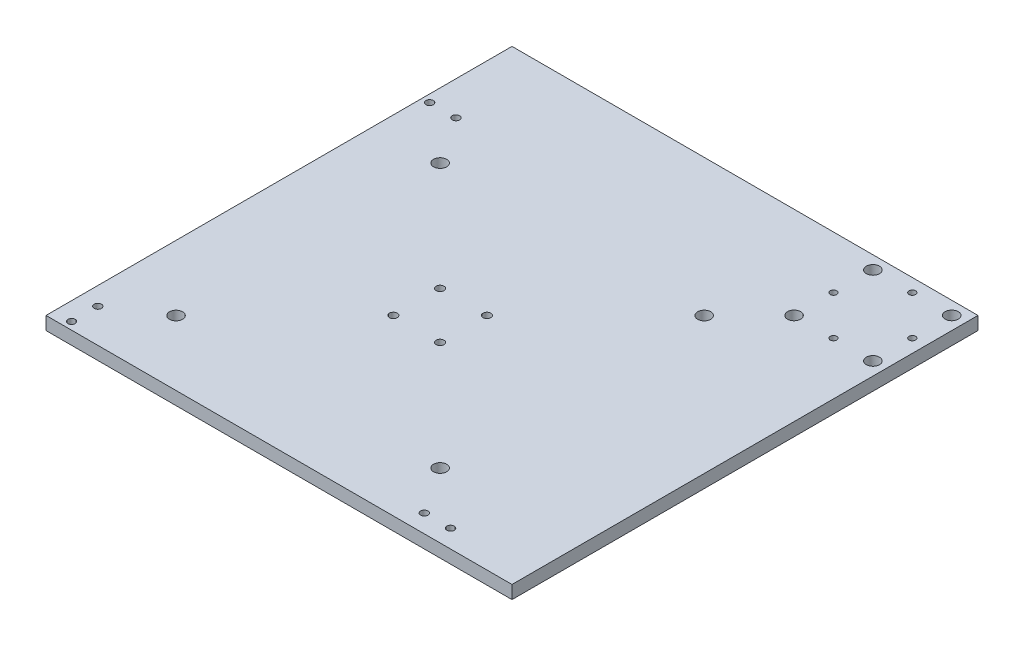
SolidWorks part; units mm, degrees
material "Perspex (TM) GS Acrylic Cast Sheet"
ref_plane "Front Plane" through (0, 0, 0) normal (0, 0, 1) x (1, 0, 0)
ref_plane "Top Plane" through (0, 0, 0) normal (0, 1, 0) x (1, 0, 0)
ref_plane "Right Plane" through (0, 0, 0) normal (1, 0, 0) x (0, 0, -1)
sketch "Sketch1" plane through (0, 0, 0) normal (0, 1, 0) x (1, 0, 0)
  line L1 (-95.25, -95.25) -> (95.25, -95.25)
  line L2 (-95.25, -95.25) -> (-95.25, 95.25)
  line L3 (-95.25, 95.25) -> (95.25, 95.25)
  line L4 (95.25, -95.25) -> (95.25, 95.25)
  line L5 (-15.875, -15.875) -> (15.875, -15.875)
  line L6 (-15.875, -15.875) -> (-15.875, 15.875)
  line L7 (-15.875, 15.875) -> (15.875, 15.875)
  line L8 (15.875, -15.875) -> (15.875, 15.875)
  circle A0 centre (-11.303, 11.303) radius 1.905
  circle A1 centre (-11.303, -11.303) radius 1.905
  circle A2 centre (11.303, 11.303) radius 1.905
  circle A3 centre (11.303, -11.303) radius 1.905
  circle A4 centre (-78.9, 86.55) radius 1.778
  circle A5 centre (-91.6, 86.55) radius 1.778
  circle A6 centre (91.6, -86.55) radius 1.778
  circle A7 centre (78.9, -86.55) radius 1.778
  circle A8 centre (-86.55, -78.9) radius 1.778
  circle A9 centre (-86.55, -91.6) radius 1.778
  circle A10 centre (0, 0) radius 6.35
  point P0 (0, 0)
  point P6 (0, 0)
  point P19 (-85.25, 92.9)
  point P24 (85.25, -92.9)
  point P29 (-92.9, -85.25)
  dimension "D5" = 4.572
  dimension "D10" = 12.7
  dimension "D18" = 12.7
  dimension "D1" = 190.5
  dimension "D2" = 190.5
  dimension "D3" = 31.75
  dimension "D4" = 31.75
  dimension "D6" = 4.572
  dimension "D7" = 4.572
  dimension "D8" = 92.9
  dimension "D9" = 85.25
  dimension "D11" = 4.572
  dimension "D12" = 6.35
  dimension "D13" = 6.35
  dimension "D14" = 92.9
  dimension "D15" = 85.25
  dimension "D16" = 6.35
  dimension "D17" = 6.35
  dimension "D19" = 85.25
  dimension "D20" = 92.9
  dimension "D21" = 6.35
  dimension "D22" = 6.35
  dimension "D23" = 12.7
extrude "Boss-Extrude1" add sketch "Sketch1" along normal blind 6.35 contours L4 L3 L2 L1 | A7 | A6 | A8 | A9 | A4 | A5 | A1 | A3 | A0 | A2
sketch "Sketch7" plane through (0, 0, 0) normal (0, -1, 0) x (1, 0, 0)
  line L0 (-130, -130) -> (78.2, -130) construction
  line L1 (130, -78.2) -> (130, 130) construction
  line L2 (-95.25, -130) -> (78.2, -130)
  line L3 (130, -78.2) -> (130, 95.25)
  line L4 (130, -78.2) -> (130, -130)
  line L5 (130, -130) -> (78.2, -130)
  line L6 (-95.25, -95.25) -> (-95.25, -130)
  line L7 (-95.25, -95.25) -> (95.25, -95.25)
  line L8 (95.25, -95.25) -> (95.25, 95.25)
  line L9 (95.25, 95.25) -> (130, 95.25)
extrude "Boss-Extrude3" add sketch "Sketch7" against normal up to surface (6.35 mm away) contours L2 L5 L4 L3 L9 L8 L7 L6 up to face at (-11.303, 6.35, -9.398)
sketch "Sketch8" plane through (0, 0, 0) normal (0, -1, 0) x (1, 0, 0)
  circle A0 centre (-63.7786, -63.7786) radius 3.175 construction
  circle A1 centre (-63.7786, 63.8746) radius 3.175 construction
  circle A2 centre (63.8746, 63.8746) radius 3.175 construction
  circle A3 centre (63.8746, -63.7786) radius 3.175 construction
  circle A4 centre (-63.7786, -63.7786) radius 3.175
  circle A5 centre (-63.7786, 63.8746) radius 3.175
  circle A6 centre (63.8746, 63.8746) radius 3.175
  circle A7 centre (63.8746, -63.7786) radius 3.175
extrude "Cut-Extrude1" cut sketch "Sketch8" against normal through all
sketch "Sketch9" plane through (0, 0, 0) normal (0, -1, 0) x (1, 0, 0)
  circle A0 centre (123.65, -123.65) radius 3.175 construction
  circle A1 centre (85.55, -85.55) radius 3.175 construction
  circle A2 centre (123.65, -85.55) radius 3.175 construction
  circle A3 centre (123.65, -123.65) radius 3.175
  circle A4 centre (85.55, -85.55) radius 3.175
  circle A5 centre (123.65, -85.55) radius 3.175
  circle A7 centre (85.55, -123.65) radius 3.175
  circle A8 centre (85.55, -123.65) radius 3.175
  dimension "D1" = 0
extrude "Cut-Extrude2" cut sketch "Sketch9" against normal through all
sketch "Sketch10" plane through (0, 0, 0) normal (0, -1, 0) x (1, 0, 0)
  circle A0 centre (104.6, -123.65) radius 1.5875 construction
  circle A1 centre (85.55, -104.6) radius 1.5875 construction
  circle A2 centre (104.6, -85.55) radius 1.5875 construction
  circle A3 centre (123.65, -104.6) radius 1.5875 construction
  circle A4 centre (104.6, -123.65) radius 1.5875
  circle A5 centre (85.55, -104.6) radius 1.5875
  circle A6 centre (104.6, -85.55) radius 1.5875
  circle A7 centre (123.65, -104.6) radius 1.5875
extrude "Cut-Extrude3" cut sketch "Sketch10" against normal through all
